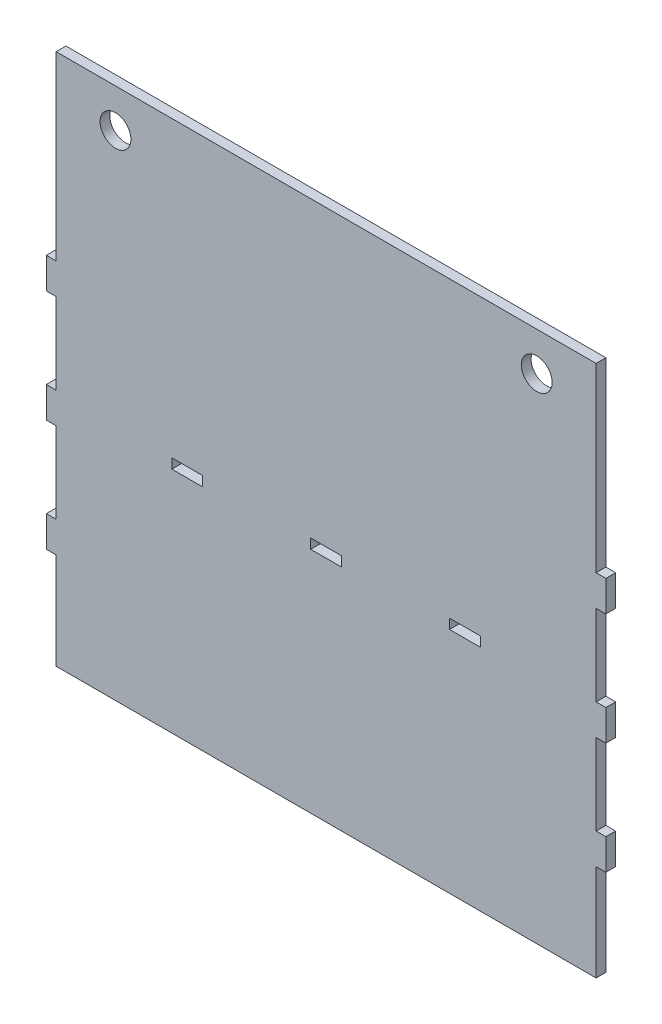
SolidWorks part; units mm, degrees
ref_plane "Alzado" through (0, 0, 0) normal (0, 0, 1) x (1, 0, 0)
ref_plane "Planta" through (0, 0, 0) normal (0, 1, 0) x (1, 0, 0)
ref_plane "Vista lateral" through (0, 0, 0) normal (1, 0, 0) x (0, 0, -1)
sketch "Croquis1" plane through (0, 0, 0) normal (0, 0, 1) x (1, 0, 0)
  line L0 (-175, 172.5) -> (175, 172.5)
  line L1 (-175, 172.5) -> (-175, -172.5)
  line L2 (-175, -172.5) -> (175, -172.5)
  line L3 (175, 172.5) -> (175, -172.5)
  point P4 (175, 0)
  point P6 (0, 172.5)
  dimension "D1" = 345
  dimension "D2" = 350
extrude "Saliente-Extruir1" add sketch "Croquis1" along normal blind 6.35
sketch "Croquis2" plane through (-175, 0, 0) normal (-1, 0, 0) x (0, 0, 1)
  line L0 (0, 172.5) -> (0, -172.5) construction
  line L1 (0, 55) -> (6.35, 55)
  line L2 (0, 55) -> (0, 35)
  line L3 (0, 35) -> (6.35, 35)
  line L4 (6.35, 55) -> (6.35, 35)
  line L5 (6.35, 172.5) -> (6.35, -172.5) construction
  line L6 (6.35, -172.5) -> (0, -172.5) construction
  line L7 (0, -17.5) -> (6.35, -17.5)
  line L8 (0, -17.5) -> (0, -37.5)
  line L9 (0, -37.5) -> (6.35, -37.5)
  line L10 (6.35, -17.5) -> (6.35, -37.5)
  line L11 (0, -90) -> (6.35, -90)
  line L12 (0, -90) -> (0, -110)
  line L13 (0, -110) -> (6.35, -110)
  line L14 (6.35, -90) -> (6.35, -110)
  dimension "D1" = 62.5
  dimension "D2" = 20
  dimension "D3" = 52.5
  dimension "D4" = 20
  dimension "D5" = 52.5
  dimension "D6" = 20
extrude "Saliente-Extruir2" add sketch "Croquis2" along normal blind 6.35
mirror "Simetría1" about plane through (0, 0, 0) normal (1, 0, 0) of "Saliente-Extruir2"
sketch "Croquis3" plane through (0, 0, 6.35) normal (0, 0, 1) x (1, 0, 0)
  line L1 (-10, -17.99) -> (10, -17.99)
  line L2 (-10, -17.99) -> (-10, -24.34)
  line L3 (-10, -24.34) -> (10, -24.34)
  line L4 (10, -17.99) -> (10, -24.34)
  line L13 (-175, -172.5) -> (175, -172.5) construction
  line L14 (80, -17.99) -> (100, -17.99)
  line L15 (80, -17.99) -> (80, -24.34)
  line L16 (80, -24.34) -> (100, -24.34)
  line L17 (100, -17.99) -> (100, -24.34)
  line L18 (-100, -17.99) -> (-80, -17.99)
  line L19 (-100, -17.99) -> (-100, -24.34)
  line L20 (-100, -24.34) -> (-80, -24.34)
  line L21 (-80, -17.99) -> (-80, -24.34)
  point P4 (0, -24.34)
  dimension "D1" = 20
  dimension "D2" = 6.35
  dimension "D3" = 148.16
extrude "Cortar-Extruir1" cut sketch "Croquis3" against normal blind 10
sketch "Croquis4" plane through (0, 0, 6.35) normal (0, 0, 1) x (1, 0, 0)
  line L0 (-136.525, 147.5) -> (136.525, 147.5) construction
  line L1 (175, 172.5) -> (-175, 172.5) construction
  circle A0 centre (-136.525, 147.5) radius 10
  circle A1 centre (136.525, 147.5) radius 10
  point P2 (0, 147.5)
  dimension "D2" = 20
  dimension "D1" = 25
  dimension "D3" = 273.05
extrude "Cortar-Extruir2" cut sketch "Croquis4" against normal through all
